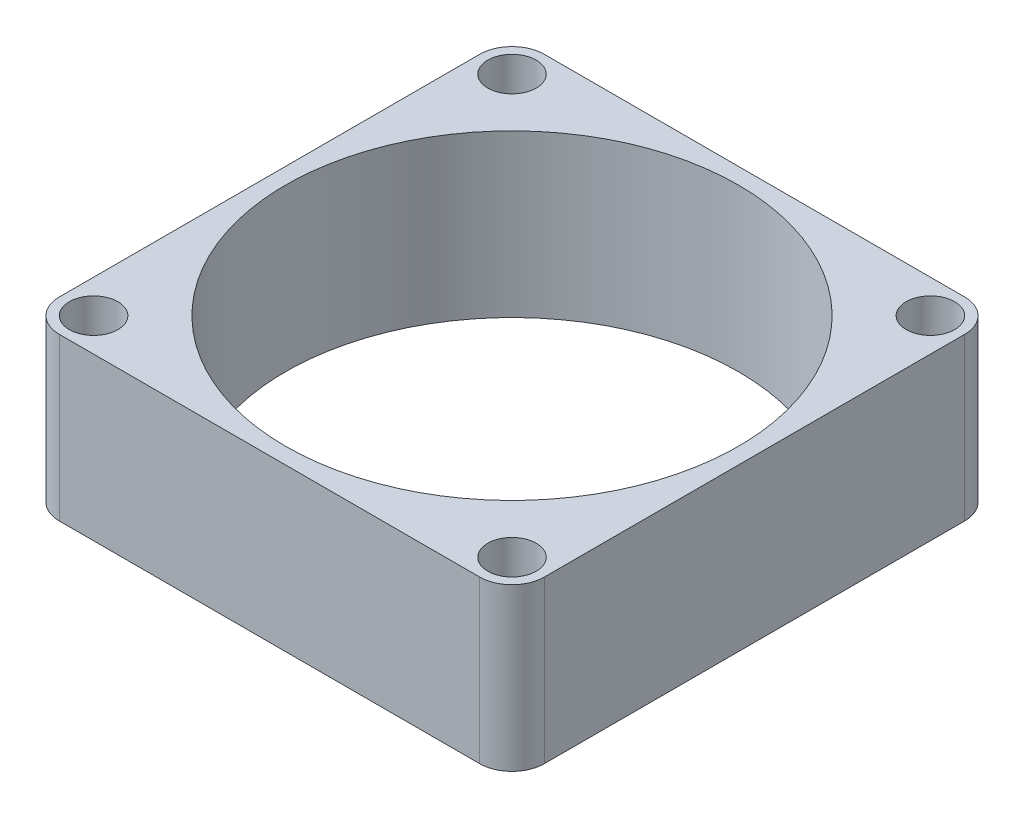
SolidWorks part; units mm, degrees
ref_plane "Piano frontale" through (0, 0, 0) normal (0, 0, 1) x (1, 0, 0)
ref_plane "Piano superiore" through (0, 0, 0) normal (0, 1, 0) x (1, 0, 0)
ref_plane "Piano destro" through (0, 0, 0) normal (1, 0, 0) x (0, 0, -1)
sketch "Schizzo1" plane through (0, 0, 0) normal (0, 1, 0) x (1, 0, 0)
  line L1 (15, -15) -> (-15, -15)
  line L2 (15, -15) -> (15, 15)
  line L3 (15, 15) -> (-15, 15)
  line L4 (-15, -15) -> (-15, 15)
  line L5 (15, -15) -> (-15, 15) construction
  line L6 (15, 15) -> (-15, -15) construction
  point P0 (0, 0)
  dimension "D1" = 30
  dimension "D2" = 30
extrude "Estrusione-Estrusione1" add sketch "Schizzo1" along normal blind 10
sketch "Schizzo2" plane through (0, 10, 0) normal (0, 1, 0) x (1, 0, 0)
  line L0 (-15, 15) -> (15, -15)
  circle A0 centre (-12.9395, 12.9395) radius 1.5
  circle A1 centre (12.9395, -12.9395) radius 1.5
  circle A2 centre (-12.9395, -12.9395) radius 1.5
  circle A3 centre (12.9395, 12.9395) radius 1.5
  dimension "D2" = 3
  dimension "D3" = 3
  dimension "D4" = 2.914
  dimension "D5" = 3
  dimension "D6" = 3
  dimension "D1" = 2.914
extrude "Taglio-Estrusione1" cut sketch "Schizzo2" against normal through all contours A0
extrude "Taglio-Estrusione2" cut sketch "Schizzo2<3>" against normal through all contours A2 | A1 | A3
sketch "Schizzo2<3>" plane through (0, 10, 0) normal (0, 1, 0) x (1, 0, 0) same geometry as "Schizzo2"
fillet "Raccordo2" radius 2 1 edges at (-15, 5, -15)
fillet "Raccordo3" radius 2 3 edges at (15, 5, -15) (15, 5, 15) (-15, 5, 15)
sketch3d "Schizzo3D1"
  circle A0 centre (0, 0, 0) radius 14
  point P2 (0, 14, 0)
extrude "Taglio-Estrusione4" cut sketch "Schizzo3D1" along direction (0, 1, 0) on the side of the normal blind 27
